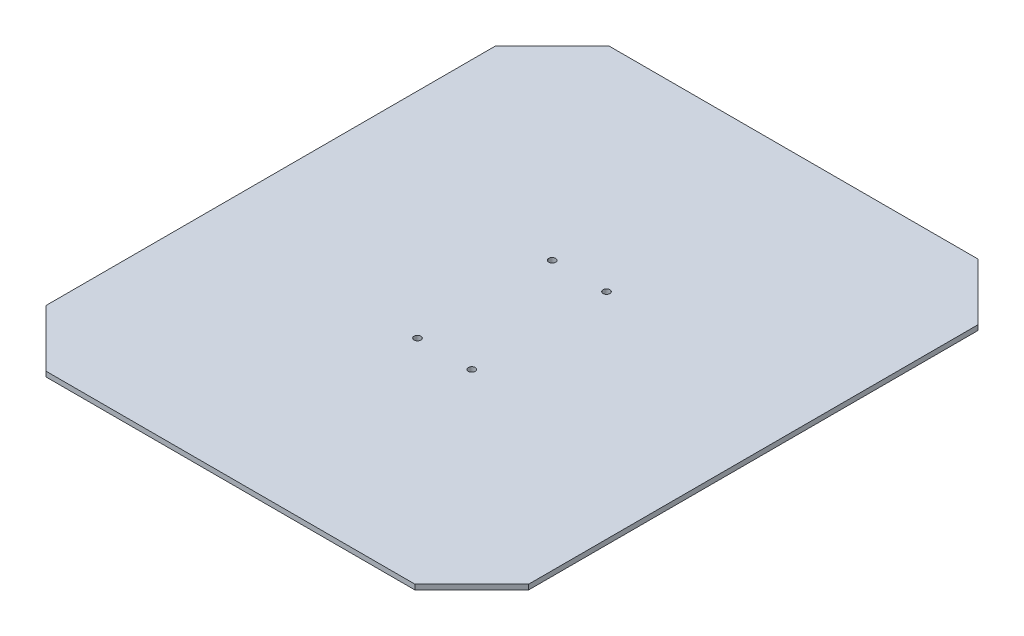
SolidWorks part; units mm, degrees
ref_plane "Front Plane" through (0, 0, 0) normal (0, 0, 1) x (1, 0, 0)
ref_plane "Top Plane" through (0, 0, 0) normal (0, 1, 0) x (1, 0, 0)
ref_plane "Right Plane" through (0, 0, 0) normal (1, 0, 0) x (0, 0, -1)
sketch "Sketch1" plane through (0, 0, 0) normal (0, 1, 0) x (1, 0, 0)
  line L0 (-61.766, 66.5353) -> (-25.845, 102.4564)
  line L1 (-61.766, 102.4564) -> (243.034, 102.4564)
  line L2 (-61.766, 102.4564) -> (-61.766, -253.1436)
  line L3 (-61.766, -253.1436) -> (243.034, -253.1436)
  line L4 (243.034, 102.4564) -> (243.034, -253.1436)
  line L5 (90.634, 95.069) -> (90.634, -294.9418) construction
  line L6 (-86.5248, -75.3436) -> (277.558, -75.3436) construction
  line L7 (243.034, 66.5353) -> (207.1129, 102.4564)
  line L8 (243.034, -217.2226) -> (207.1129, -253.1436)
  line L9 (-61.766, -217.2226) -> (-25.845, -253.1436)
  point P8 (90.634, 102.4564)
  point P11 (-61.766, -75.3436)
  dimension "D1" = 304.8
  dimension "D2" = 355.6
  dimension "D3" = 45
  dimension "D4" = 50.8
extrude "Boss-Extrude1" add sketch "Sketch1" along normal blind 3.175 contours L2 L9 L3 L8 L4 L7 L1 L0 region at (90.634, 0, 75.3436)
sketch "Sketch2" plane through (0, 3.175, 0) normal (0, 1, 0) x (1, 0, 0)
  line L0 (90.634, 102.4564) -> (90.634, -287.8465) construction
  line L1 (-25.845, 102.4564) -> (207.1129, 102.4564) construction
  line L2 (243.034, -75.3436) -> (-158.2106, -75.3436) construction
  line L3 (243.034, 66.5353) -> (243.034, -217.2226) construction
  circle A0 centre (73.362, -32.6716) radius 2.159
  circle A1 centre (107.652, -32.6716) radius 2.159
  circle A2 centre (73.362, -117.7616) radius 2.159
  circle A3 centre (107.652, -117.7616) radius 2.159
  point P16 (0, 0)
  point P17 (0, 0)
  point P18 (0, 0)
  point P19 (0, 0)
  dimension "D5" = 4.318
  dimension "D6" = 4.318
  dimension "D7" = 4.318
  dimension "D8" = 4.318
  dimension "D1" = 17.272
  dimension "D2" = 34.29
  dimension "D3" = 85.09
  dimension "D4" = 42.672
extrude "Cut-Extrude1" cut sketch "Sketch2" against normal through all
